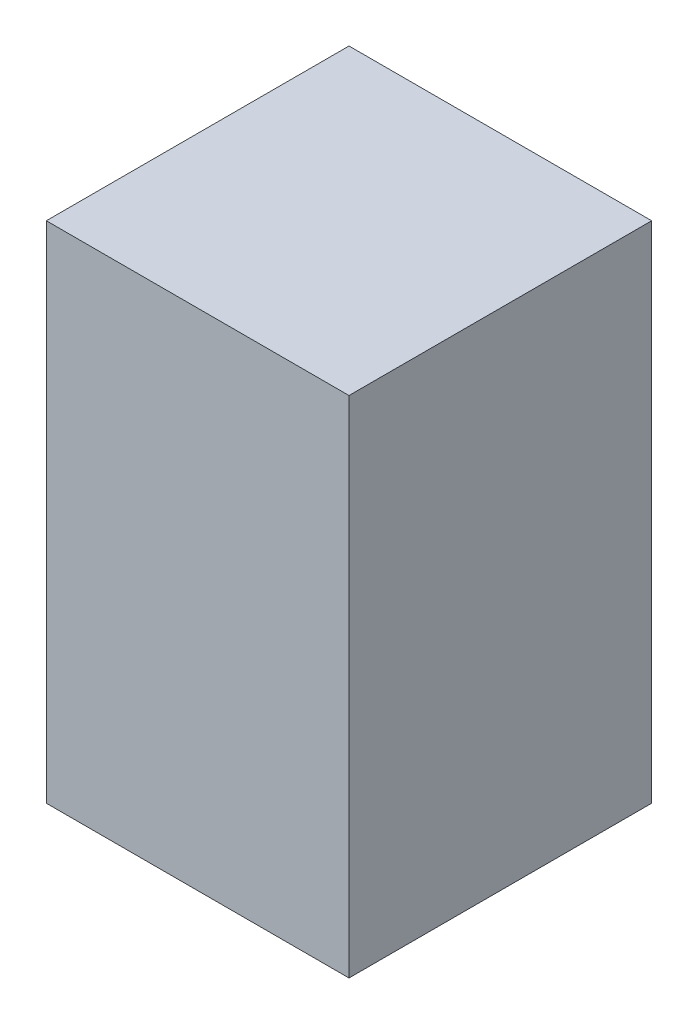
SolidWorks part; units mm, degrees
ref_plane "Front Plane" through (0, 0, 0) normal (0, 0, 1) x (1, 0, 0)
ref_plane "Top Plane" through (0, 0, 0) normal (0, 1, 0) x (1, 0, 0)
ref_plane "Right Plane" through (0, 0, 0) normal (1, 0, 0) x (0, 0, -1)
sketch "Sketch3" plane through (0, 0, 0) normal (0, 0, 1) x (1, 0, 0)
  line L1 (-15, -25) -> (15, -25)
  line L2 (-15, -25) -> (-15, 25)
  line L3 (-15, 25) -> (15, 25)
  line L4 (15, -25) -> (15, 25)
  line L5 (-15, -25) -> (15, 25) construction
  line L6 (-15, 25) -> (15, -25) construction
  point P0 (0, 0)
  dimension "D1" = 30
  dimension "D2" = 50
extrude "Boss-Extrude1" add sketch "Sketch3" along normal blind 30
